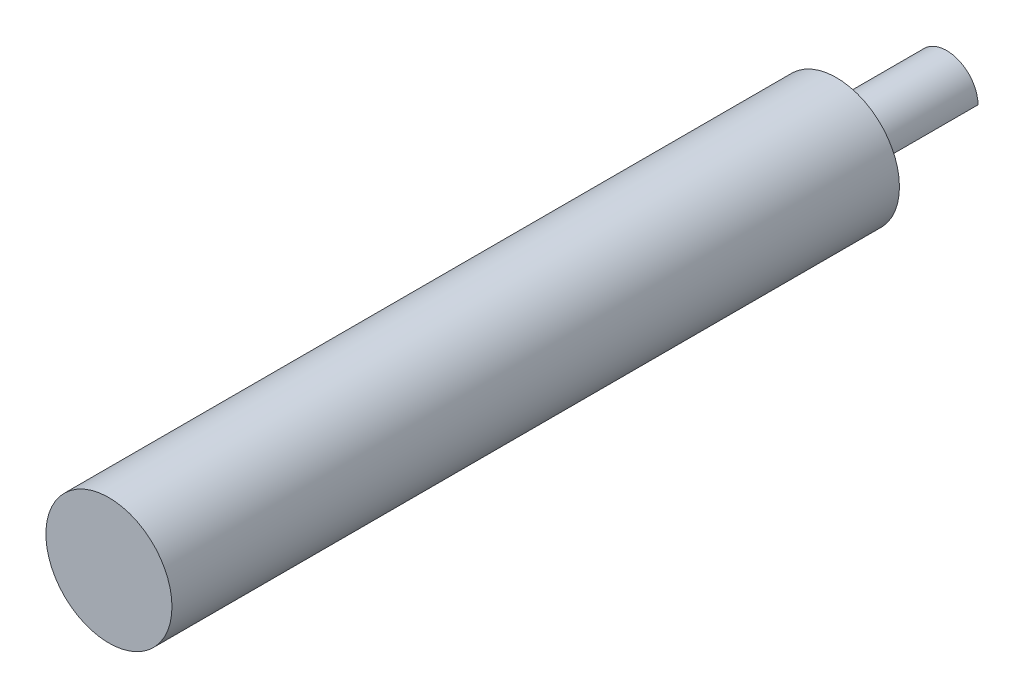
SolidWorks part; units mm, degrees
ref_plane "Front Plane" through (0, 0, 0) normal (0, 0, 1) x (1, 0, 0)
ref_plane "Top Plane" through (0, 0, 0) normal (0, 1, 0) x (1, 0, 0)
ref_plane "Right Plane" through (0, 0, 0) normal (1, 0, 0) x (0, 0, -1)
sketch "Sketch1" plane through (0, 0, 0) normal (0, 0, 1) x (1, 0, 0)
  circle A0 centre (0, 0) radius 3.1623
  dimension "D1" = 6.3246
extrude "Boss-Extrude1" add sketch "Sketch1" along normal blind 11.0998
sketch "Sketch2" plane through (0, 0, 0) normal (0, 0, -1) x (-1, 0, 0)
  line L0 (0.0012, -3.1623) -> (-3.1623, 0.0012)
  circle A0 centre (0, 0) radius 3.1623 construction
  dimension "D1" = 2.2352
extrude "Cut-Extrude1" cut sketch "Sketch2" against normal through all and the other way through all
sketch "Sketch3" plane through (0, 0, 11.0998) normal (0, 0, 1) x (1, 0, 0)
  circle A0 centre (0, 0) radius 6.35
  dimension "D1" = 12.7
extrude "Boss-Extrude2" add sketch "Sketch3" along normal blind 73.279
sketch "Sketch5" plane through (0, 0, 84.3788) normal (0, 0, 1) x (1, 0, 0)
  circle A0 centre (0, 0) radius 6.35
fillet "Fillet1" radius 1.27 2 edges at (-2.2361, 2.2361, 11.0998) (1.5805, -1.5805, 11.0998) type face fillet first side face at (6.35, 0, 11.0998) second side face at (-0.3278, 0.3278, 5.5499) second side face at (1.5805, -1.5805, 5.5499)
